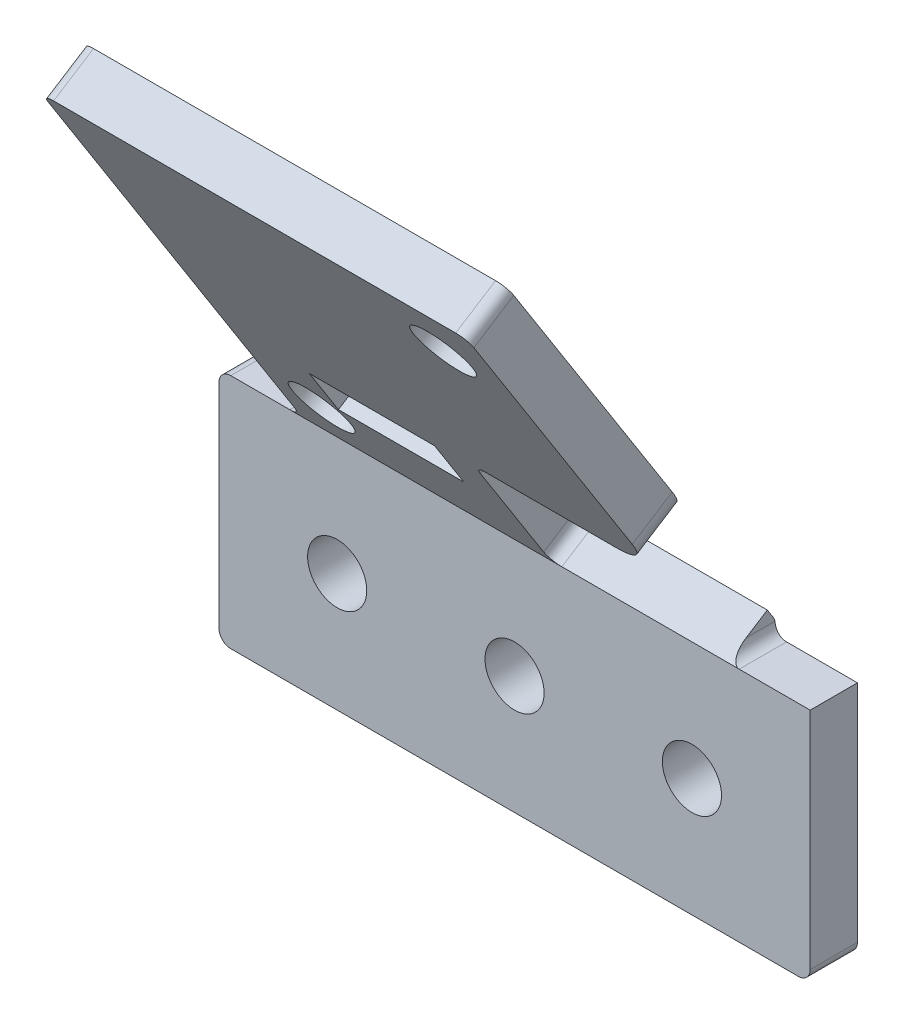
SolidWorks part; units mm, degrees
ref_plane "前视基准面" through (0, 0, 0) normal (0, 0, 1) x (1, 0, 0)
ref_plane "上视基准面" through (0, 0, 0) normal (0, 1, 0) x (1, 0, 0)
ref_plane "右视基准面" through (0, 0, 0) normal (1, 0, 0) x (0, 0, -1)
sketch "草图1" plane through (0, 0, 0) normal (0, 0, 1) x (1, 0, 0)
  line L1 (25, -10) -> (-25, -10)
  line L2 (25, -10) -> (25, 10)
  line L3 (25, 10) -> (-25, 10)
  line L4 (-25, -10) -> (-25, 10)
  line L5 (25, -10) -> (-25, 10) construction
  line L6 (25, 10) -> (-25, -10) construction
  point P0 (0, 0)
  dimension "D1" = 20
  dimension "D2" = 50
extrude "凸台-拉伸1" add sketch "草图1" along normal blind 4
sketch "草图4" plane through (0, 0, 0) normal (1, 0, 0) x (0, 0, -1)
  line L0 (-4, 10) -> (-25.9804, 44.6101)
  line L1 (-25.9804, 44.6101) -> (-22.6038, 46.7546)
  line L2 (-22.6038, 46.7546) -> (0.0489, 11.0858)
  line L3 (0.0489, 11.0858) -> (0, 10)
  line L4 (-4, 10) -> (0, 10)
  dimension "D1" = 145
  dimension "D2" = 41
  dimension "D3" = 4
extrude "凸台-拉伸2" add sketch "草图4" along normal mid plane 36
sketch "草图5" plane through (0, 1.0639, -1.6752) normal (0, -0.5361, 0.8441) x (1, 0, 0)
  line L0 (18, 51.5859) -> (-18, 10.5859) construction
  circle A2 centre (12.7216, 45.5744) radius 1.5
  circle A3 centre (-13.6705, 15.5168) radius 1.5
  dimension "D1" = 8
  dimension "D2" = 3
  dimension "D3" = 3
  dimension "D4" = 40
extrude "切除-拉伸1" cut sketch "草图5" against normal through all contours A2 | A2 | A3 | A3 region at (12.7216, 39.5355, 22.7576) region at (-13.6705, 14.1624, 6.6435)
sketch "草图6" plane through (0, 1.0639, -1.6752) normal (0, -0.5361, 0.8441) x (1, 0, 0)
  line L1 (18, 10.5859) -> (3, 10.5859)
  line L2 (18, 10.5859) -> (18, 22.5859)
  line L3 (18, 22.5859) -> (3, 22.5859)
  line L4 (3, 10.5859) -> (3, 22.5859)
  dimension "D1" = 15
  dimension "D2" = 12
extrude "切除-拉伸2" cut sketch "草图6" against normal through all
fillet "圆角1" radius 1 2 edges at (3, 11.0722, 2.3117) (3, 21.202, 8.745)
fillet "圆角2" radius 1 7 edges at (25, -10, 2) (-25, -10, 2) (-18, 45.6824, 24.2921) (18, 45.6824, 24.2921) (-25, 10, 2) (-18, 10, 2) (18, 10, 2)
fillet "圆角3" radius 1 1 edges at (0, 11.0858, -0.0489)
sketch "草图7" plane through (0, 1.0639, -1.6752) normal (0, -0.5361, 0.8441) x (1, 0, 0)
  circle A0 centre (12.7216, 45.5744) radius 2.5
  circle A1 centre (-13.6705, 15.5168) radius 2.5
  dimension "D1" = 5
  dimension "D2" = 5
extrude "切除-拉伸3" cut sketch "草图7" against normal blind 2
sketch "草图8" plane through (0, 0, 4) normal (0, 0, 1) x (1, 0, 0)
  line L0 (0, -10) -> (0, 0) construction
  line L1 (-24, -10) -> (24, -10) construction
  circle A0 centre (0, 0) radius 2.5
  circle A1 centre (15, 0) radius 2.5
  circle A2 centre (-15, 0) radius 2.5
  dimension "D1" = 5
  dimension "D2" = 10
  dimension "D3" = 2
  dimension "D4" = 2
extrude "切除-拉伸4" cut sketch "草图8" against normal through all
sketch "草图9" plane through (0, 1.0639, -1.6752) normal (0, -0.5361, 0.8441) x (1, 0, 0)
  line L1 (-11, 21.5859) -> (-1, 21.5859)
  line L2 (-11, 21.5859) -> (-11, 17.5859)
  line L3 (-11, 17.5859) -> (-1, 17.5859)
  line L4 (-1, 21.5859) -> (-1, 17.5859)
  line L5 (-0.7, 17.2859) -> (-11.3, 17.2859)
  line L6 (-0.7, 17.2859) -> (-0.7, 21.8859)
  line L7 (-0.7, 21.8859) -> (-11.3, 21.8859)
  line L8 (-11.3, 17.2859) -> (-11.3, 21.8859)
  line L9 (-0.7, 17.2859) -> (-11.3, 21.8859) construction
  line L10 (-0.7, 21.8859) -> (-11.3, 17.2859) construction
  point P6 (-6, 19.5859)
  dimension "D1" = 0.3
  dimension "D2" = 0.3
  dimension "D3" = 0.3
  dimension "D4" = 0.3
extrude "切除-拉伸5" cut sketch "草图9" against normal blind 10 contours L7 L8 L5 L6
fillet "圆角4" radius 3 1 edges at (18, 21.202, 8.745)
